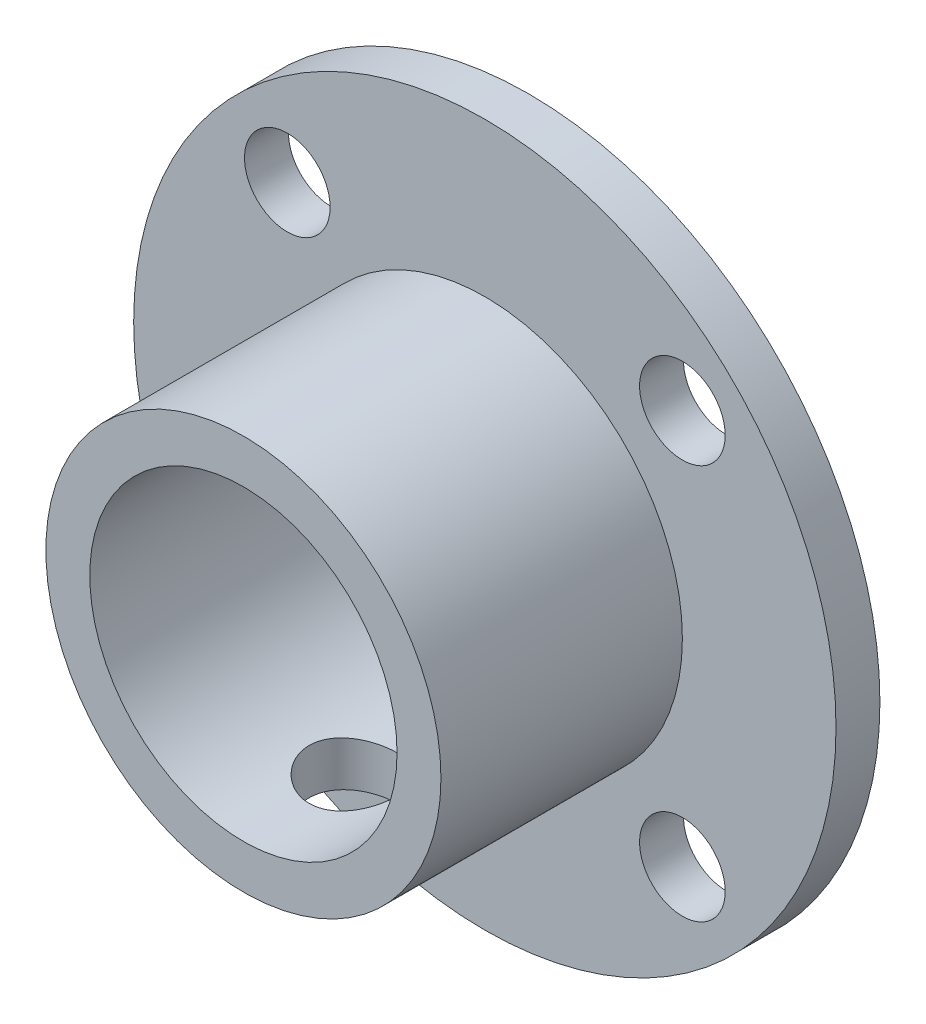
SolidWorks part; units mm, degrees
ref_plane "Front Plane" through (0, 0, 0) normal (1, 0, 0) x (0, 1, 0)
ref_plane "Top Plane" through (0, 0, 0) normal (0, 0, 1) x (0, 1, 0)
ref_plane "Right Plane" through (0, 0, 0) normal (0, 1, 0) x (-1, 0, 0)
sketch "Sketch1" plane through (0, 0, 0) normal (0, 0, 1) x (0, 1, 0)
  line L1 (9, -9) -> (-9, -9) construction
  line L2 (9, -9) -> (9, 9) construction
  line L3 (9, 9) -> (-9, 9) construction
  line L4 (-9, -9) -> (-9, 9) construction
  line L5 (9, -9) -> (-9, 9) construction
  line L6 (9, 9) -> (-9, -9) construction
  circle A0 centre (0, 0) radius 16
  circle A3 centre (-9, 9) radius 1.95
  circle A4 centre (-9, -9) radius 1.95
  circle A5 centre (9, -9) radius 1.95
  circle A6 centre (9, 9) radius 1.95
  circle A7 centre (0, 0) radius 9
  circle A8 centre (0, 0) radius 7
  dimension "D1" = 32
  dimension "D2" = 3.9
  dimension "D3" = 18
  dimension "D4" = 18
  dimension "D5" = 14
extrude "Boss-Extrude1" add sketch "Sketch1" along normal blind 2 contours A0 A7 A6 A5 A4 A3 | A7 A8 region at (0, -15.5475, 0) region at (0, -8.7454, 0)
extrude "Boss-Extrude2" add sketch "Sketch1<3>" along normal blind 13 contours A7 A8 region at (0, -8.7454, 0)
sketch "Sketch1<3>" plane through (0, 0, 0) normal (0, 0, 1) x (0, 1, 0) same geometry as "Sketch1"
sketch "Sketch2" plane through (0, 0, 0) normal (0, 1, 0) x (-1, 0, 0)
  circle A0 centre (0, 8) radius 2
  point P2 (0, 0)
  dimension "D1" = 4
  dimension "D2" = 8
extrude "Cut-Extrude1" cut sketch "Sketch2" against normal blind 13
